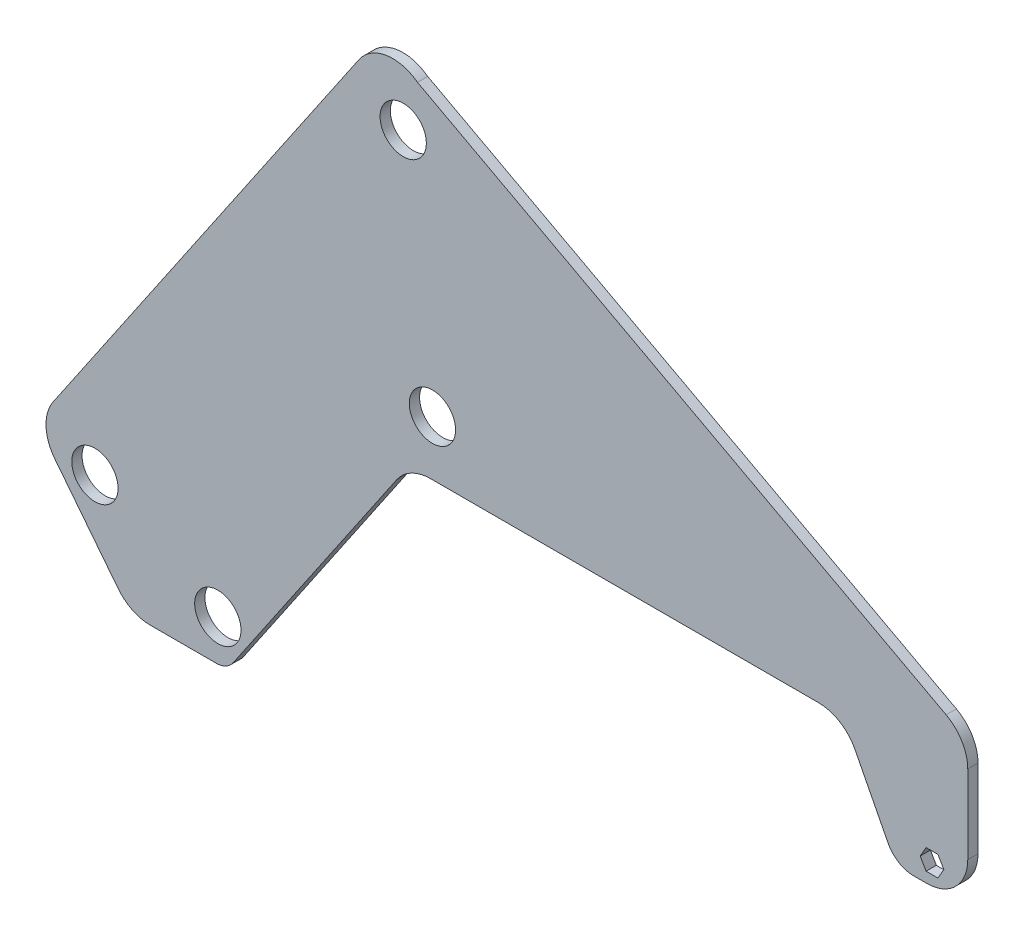
SolidWorks part; units mm, degrees
other "Markup1"
sketch "Sketch1" plane through (-441.7893, 331.8239, 6.35) normal (-0.0431, 0.0102, 0.999) x (0.9985, 0.0354, 0.0427)
sketch "Sketch2" plane through (-413.6701, 343.933, 6.35) normal (-0.0431, 0.0102, 0.999) x (0.9985, 0.0354, 0.0427)
sketch "Sketch3" plane through (-436.3774, 318.5567, 6.35) normal (-0.0431, 0.0102, 0.999) x (0.9985, 0.0354, 0.0427)
sketch "Sketch5" plane through (-436.3774, 318.5567, 6.35) normal (-0.0431, 0.0102, 0.999) x (0.9985, 0.0354, 0.0427)
sketch "Sketch7" plane through (-430.3226, 318.5567, 6.35) normal (-0.0431, 0.0102, 0.999) x (0.9985, 0.0354, 0.0427)
sketch "Sketch9" plane through (-430.3226, 318.5567, 6.35) normal (-0.0431, 0.0102, 0.999) x (0.9985, 0.0354, 0.0427)
sketch "Sketch11" plane through (-430.3226, 318.5567, 6.35) normal (-0.0431, 0.0102, 0.999) x (0.9985, 0.0354, 0.0427)
other "Markup2"
sketch "Sketch4" plane through (102.4721, 318.5567, 6.35) normal (0.9364, 0.1073, 0.3342) x (0.3416, -0.0598, -0.9379)
sketch "Sketch6" plane through (102.4721, 318.5567, 6.35) normal (0.9364, 0.1073, 0.3342) x (0.3416, -0.0598, -0.9379)
sketch "Sketch8" plane through (141.2086, 318.5567, 6.35) normal (0.9364, 0.1073, 0.3342) x (0.3416, -0.0598, -0.9379)
sketch "Sketch10" plane through (141.2086, 318.5567, 6.35) normal (0.9364, 0.1073, 0.3342) x (0.3416, -0.0598, -0.9379)
sketch "Sketch12" plane through (141.2086, 318.5567, 6.35) normal (0.9364, 0.1073, 0.3342) x (0.3416, -0.0598, -0.9379)
ref_plane "Front Plane" through (0, 0, 0) normal (0, 0, 1) x (1, 0, 0)
ref_plane "Top Plane" through (0, 0, 0) normal (0, 1, 0) x (1, 0, 0)
ref_plane "Right Plane" through (0, 0, 0) normal (1, 0, 0) x (0, 0, -1)
sketch "Model" plane through (0, 0, 0) normal (0, 0, 1) x (1, 0, 0)
  line L1 (-191.9011, 104.6502) -> (-112.96, 104.6502)
  line L3 (-314.2383, -55.3595) -> (-212.8994, 93.5413)
  line L4 (-236.3032, 307.4477) -> (-425.9209, 28.8361)
  line L5 (-424.8981, -1.1437) -> (-385.5815, -51.2028)
  line L13 (126.3831, 53.8502) -> (122.717, 60.2002)
  line L14 (122.717, 60.2002) -> (115.3846, 60.2002)
  line L15 (115.3846, 60.2002) -> (111.7185, 53.8502)
  line L16 (111.7185, 53.8502) -> (115.3846, 47.5002)
  line L17 (115.3846, 47.5002) -> (122.717, 47.5002)
  line L18 (122.717, 47.5002) -> (126.3831, 53.8502)
  line L19 (-365.606, -60.914) -> (-324.7375, -60.914)
  line L20 (-871.0211, -88.854) -> (370.1019, -88.854) construction
  line L22 (141.2086, 66.5502) -> (141.2086, 78.8846)
  line L27 (107.6196, 41.1502) -> (115.8086, 41.1502)
  line L28 (-399.9752, 2.586) -> (-323.7752, -35.514) construction
  line L29 (-323.7752, -35.514) -> (-190.7071, 138.5169) construction
  line L30 (-190.7071, 138.5169) -> (-208.8329, 283.4378) construction
  line L31 (-208.8329, 283.4378) -> (-399.9752, 2.586) construction
  line L32 (91.8004, 50.8135) -> (71.26, 90.8456)
  line L33 (48.6612, 104.6502) -> (-11.3966, 104.6502)
  line L34 (141.2086, 78.8846) -> (141.2086, 115.3033)
  line L35 (127.8091, 137.6897) -> (-86.3327, 252.4836)
  line L36 (-112.96, 104.6502) -> (-68.51, 104.6502)
  line L37 (-122.3008, 271.7648) -> (-85.2777, 251.9181)
  line L40 (-68.51, 104.6502) -> (-2.1388, 104.6502)
  line L41 (-122.3008, 271.7648) -> (-199.9496, 313.3896)
  arc A3 (121.2475, 59.8082) -> (121.352, 60.2002) centre (96.7586, 66.5502) ccw
  circle A9 centre (-323.7752, -35.514) radius 14.351
  circle A10 centre (-399.9752, 2.586) radius 14.351
  circle A12 centre (-190.7071, 138.5169) radius 14.351
  arc A15 (107.6196, 41.1502) -> (91.8004, 50.8135) centre (107.6196, 58.9302) cw
  arc A21 (-191.9011, 104.6502) -> (-212.8994, 93.5413) centre (-191.9011, 79.2502) ccw
  circle A22 centre (-208.8329, 283.4378) radius 14.351
  circle A24 centre (119.0508, 53.8502) radius 6.35 construction
  arc A31 (-324.7375, -60.914) -> (-314.2383, -55.3595) centre (-324.7375, -48.214) ccw
  arc A40 (114.7422, 48.6129) -> (115.0458, 48.9225) centre (96.7586, 66.5502) ccw
  arc A43 (115.8086, 41.1502) -> (141.2086, 66.5502) centre (115.8086, 66.5502) ccw
  arc A44 (-236.3032, 307.4477) -> (-199.9496, 313.3896) centre (-215.305, 293.1567) cw
  arc A45 (-365.606, -60.914) -> (-385.5815, -51.2028) centre (-365.606, -35.514) cw
  arc A46 (71.26, 90.8456) -> (48.6612, 104.6502) centre (48.6612, 79.2502) ccw
  arc A47 (141.2086, 115.3033) -> (127.8091, 137.6897) centre (115.8086, 115.3033) ccw
  arc A48 (-424.8981, -1.1437) -> (-425.9209, 28.8361) centre (-404.9226, 14.5451) cw
  ellipse E0 centre (-551.1692, 173.9527) end of major axis (-591.2054, 216.0961) minor radius 17.278
  point P31 (-177.5612, 330.9695)
  point P34 (100.2935, -12.8222)
  point P43 (-377.9543, -60.914)
  point P55 (96.7586, 41.1502)
  point P59 (174.831, 53.8502)
  point P60 (-205.3388, 104.6502)
  point P64 (-436.3774, 13.472)
  dimension "D3" = 38.1
  dimension "D4" = 104.6502
  dimension "D5" = 76.2
  dimension "D6" = 44.45
  dimension "D7" = 12.7
  dimension "D8" = 28.702
  dimension "D11" = 139.7
  dimension "D12" = 27.94
  dimension "D21" = 124.238
  dimension "D13" = 12.7
  dimension "D16" = 355.6
  dimension "D23" = 25.4
  dimension "D24" = 25.4
  dimension "D26" = 25.4
  dimension "D14" = 406.4
  dimension "D20" = 254
  dimension "D29" = 25.4
  dimension "D31" = 25.4
  dimension "D25" = 88.9
  dimension "D30" = 17.78
  dimension "D32" = 25.4
  dimension "D33" = 25.4
  dimension "D9" = 19.05
  dimension "D10" = 146.05
  dimension "D15" = 33.8667
  dimension "D17" = 339.725
  dimension "D18" = 219.075
  dimension "D19" = 50.8
  dimension "D22" = 25.4
  dimension "D27" = 53.2168
  dimension "D28" = 12.7
extrude "Boss-Extrude1" add sketch "Model" along normal blind 6.35 contours L5 L3 L1 L4 A22 A9 A10 A12 region at (-206.9871, 107.7659, 0)
